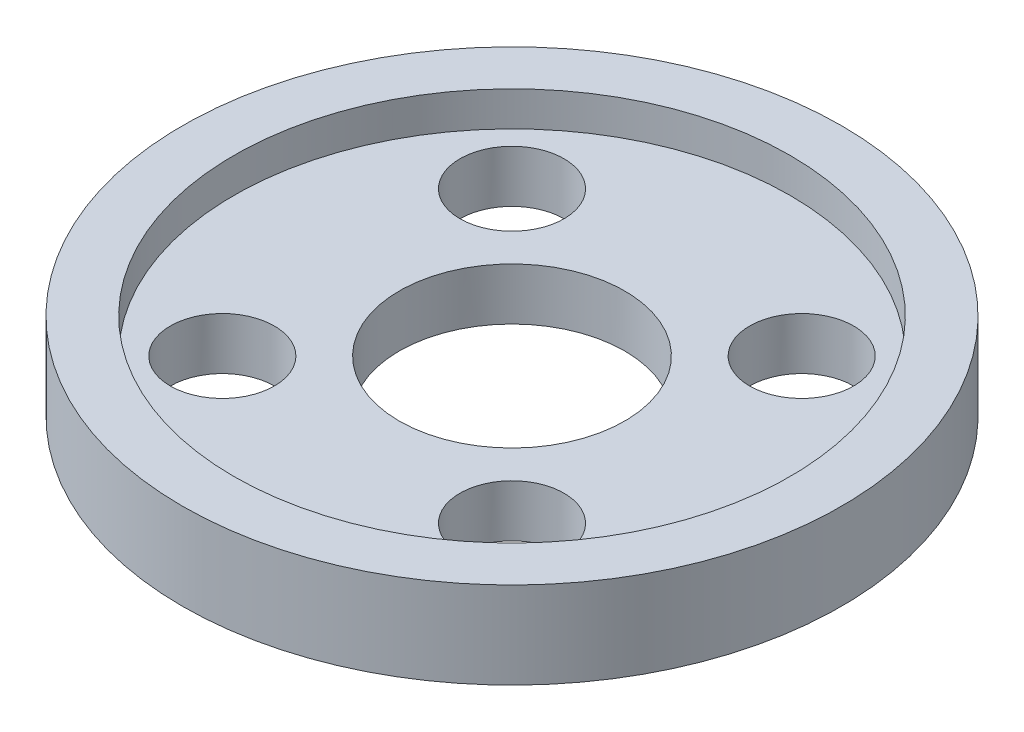
SolidWorks part; units mm, degrees
ref_plane "Front Plane" through (0, 0, 0) normal (0, 0, 1) x (1, 0, 0)
ref_plane "Top Plane" through (0, 0, 0) normal (0, 1, 0) x (1, 0, 0)
ref_plane "Right Plane" through (0, 0, 0) normal (1, 0, 0) x (0, 0, -1)
sketch "Sketch1" plane through (0, 0, 0) normal (0, 1, 0) x (1, 0, 0)
  circle A0 centre (0, 0) radius 105
  dimension "D1" = 210
extrude "Boss-Extrude1" add sketch "Sketch1" along normal blind 40
sketch "Sketch2" plane through (0, 40, 0) normal (0, 1, 0) x (1, 0, 0)
  line L0 (0, 0) -> (0, 90)
  line L1 (0, 0) -> (-38.0356, 81.5677)
  circle A2 centre (0, 0) radius 90
  circle A3 centre (0, 0) radius 22.5
  dimension "D1" = 45
  dimension "D3" = 180
  dimension "D2" = 25
extrude "Cut-Extrude1" [suppressed] cut sketch "Sketch2" against normal blind 40
fillet "Fillet1" [suppressed] radius 6
sketch "Sketch3" plane through (0, 40, 0) normal (0, 1, 0) x (1, 0, 0)
  circle A0 centre (0, 0) radius 6.5
  dimension "D1" = 13
extrude "Cut-Extrude2" cut sketch "Sketch3" against normal blind 40
pattern_circular "CirPattern1" [suppressed] count 7 over 360 reverse direction yes of bodies 104
ref_plane "Plane1" through (0, 20, 0) normal (0, 1, 0) x (1, 0, 0)
sketch "Sketch4" plane through (0, 40, 0) normal (0, 1, 0) x (1, 0, 0)
  circle A0 centre (0, 0) radius 16.035
  dimension "D1" = 32.07
extrude "Cut-Extrude3" cut sketch "Sketch4" against normal blind 5
sketch "Sketch8" plane through (0, 35, 0) normal (0, 1, 0) x (1, 0, 0)
  circle A0 centre (-8.35, 8.35) radius 3
  circle A1 centre (8.35, 8.35) radius 3
  circle A2 centre (8.35, -8.35) radius 3
  circle A3 centre (-8.35, -8.35) radius 3
  point P0 (8.35, 8.35)
  point P2 (-8.35, 8.35)
  point P4 (-8.35, -8.35)
  point P6 (8.35, -8.35)
  dimension "D1" = 8.35
  dimension "D5" = 6
  dimension "D2" = 8.35
  dimension "D3" = 8.35
  dimension "D4" = 8.35
extrude "Cut-Extrude6" cut sketch "Sketch8" against normal blind 44.5
sketch "Sketch11" plane through (0, 40, 0) normal (0, 1, 0) x (1, 0, 0)
  circle A0 centre (0, 0) radius 26.035
  circle A1 centre (0, 0) radius 90
  circle A2 centre (0, 0) radius 105 construction
  circle A3 centre (0, 0) radius 16.035 construction
  dimension "D1" = 15
  dimension "D2" = 10
extrude "Cut-Extrude8" cut sketch "Sketch11" against normal blind 10
ref_plane "Plane2" through (0, 20, 0) normal (0, 1, 0) x (1, 0, 0)
ref_axis "Axis1" through (0, 0, 0) along (0, 1, 0)
sketch "Sketch12" plane through (0, 40, 0) normal (0, 1, 0) x (1, 0, 0)
  circle A0 centre (0, 0) radius 108
  circle A1 centre (0, 0) radius 105
  circle A2 centre (0, 0) radius 105 construction
  dimension "D1" = 216
  dimension "D2" = 210
extrude "Boss-Extrude2" add sketch "Sketch12" against normal blind 3
ref_plane "Plane3" through (0, 20, 0) normal (0, -1, 0) x (-1, 0, 0)
mirror "Mirror1" about plane through (0, 20, 0) normal (0, -1, 0) of "Boss-Extrude2"
sketch "Sketch13" plane through (0, 40, 0) normal (0, 1, 0) x (1, 0, 0)
  circle A0 centre (0, 0) radius 19
  circle A1 centre (0, 0) radius 108
  dimension "D1" = 38
extrude "Cut-Extrude9" cut sketch "Sketch13" against normal through all
sketch "Sketch14" plane through (0, 0, 0) normal (0, -1, 0) x (1, 0, 0)
  circle A0 centre (0, 0) radius 27.4445
extrude "Cut-Extrude10" cut sketch "Sketch14" against normal blind 32
sketch "Sketch15" plane through (0, 40, 0) normal (0, 1, 0) x (1, 0, 0)
  circle A0 centre (0, 0) radius 19
extrude "Cut-Extrude11" cut sketch "Sketch15" against normal blind 3
